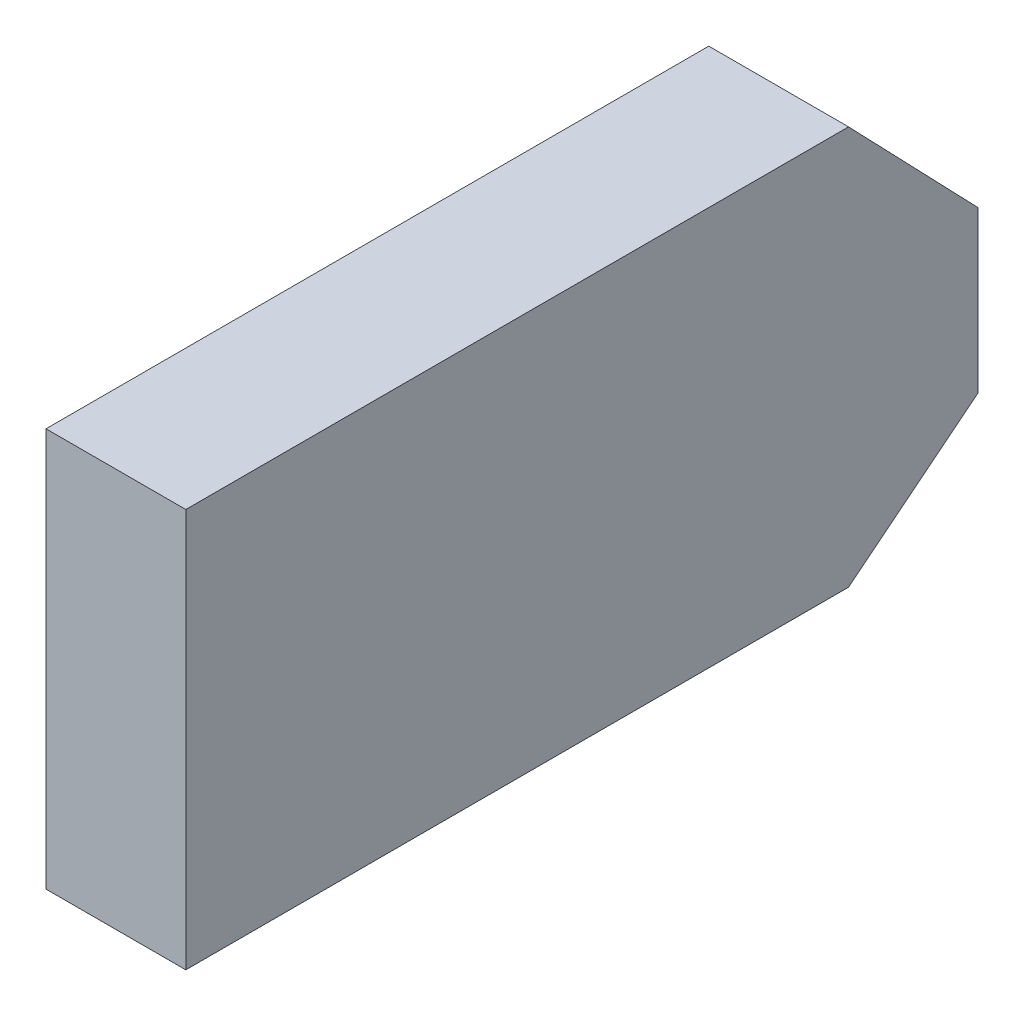
SolidWorks part; units mm, degrees
ref_plane "Front Plane" through (0, 0, 0) normal (0, 0, 1) x (1, 0, 0)
ref_plane "Top Plane" through (0, 0, 0) normal (0, 1, 0) x (1, 0, 0)
ref_plane "Right Plane" through (0, 0, 0) normal (1, 0, 0) x (0, 0, -1)
sketch "Sketch1" plane through (0, 0, 0) normal (1, 0, 0) x (0, 0, -1)
  line L0 (-18.7192, -107.2089) -> (124.6222, -107.2089) construction
sketch "Sketch2" plane through (0, 0, 0) normal (1, 0, 0) x (0, 0, -1)
  line L0 (0, 0) -> (0, 77)
  line L1 (0, 77) -> (128, 77)
  line L2 (128, 77) -> (153, 51)
  line L3 (153, 51) -> (153, 20)
  line L4 (153, 20) -> (128, 0)
  line L5 (128, 0) -> (0, 0)
  line L6 (0, 77) -> (0, 104) construction
  line L7 (128, 77) -> (145, 77) construction
  line L8 (145, 77) -> (145, 104) construction
  circle A0 centre (10.5, 90.5) radius 3.6414 construction
  circle A1 centre (23, 90.5) radius 3.5671 construction
  circle A2 centre (36, 90.5) radius 3.2818 construction
  point P16 (0, 90.5)
  dimension "D1" = 77
  dimension "D2" = 27
  dimension "D3" = 153
  dimension "D4" = 20
  dimension "D5" = 128
  dimension "D6" = 128
  dimension "D7" = 31
  dimension "D8" = 17
  dimension "D9" = 27
  dimension "D10" = 10.5
  dimension "D11" = 23
  dimension "D12" = 36
extrude "Boss-Extrude1" add sketch "Sketch2" along normal blind 27
